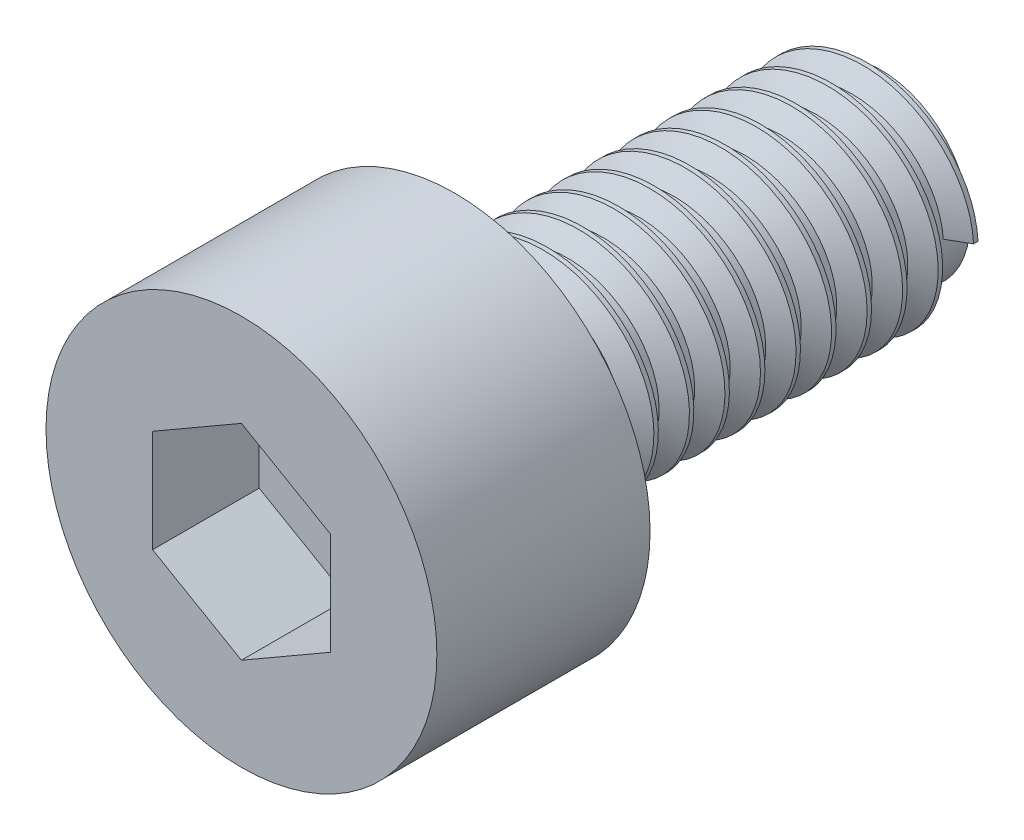
SolidWorks part; units mm, degrees
material "Cast Carbon Steel"
ref_plane "Front Plane" through (0, 0, 0) normal (0, 0, 1) x (1, 0, 0)
ref_plane "Top Plane" through (0, 0, 0) normal (0, 1, 0) x (1, 0, 0)
ref_plane "Right Plane" through (0, 0, 0) normal (1, 0, 0) x (0, 0, -1)
sketch "Sketch1" plane through (0, 0, 0) normal (0, 0, 1) x (1, 0, 0)
  circle A0 centre (0, 0) radius 2.75
  dimension "D1" = 5.5
extrude "Boss-Extrude1" add sketch "Sketch1" along normal blind 3
sketch "Sketch2" plane through (0, 0, 0) normal (0, 0, -1) x (-1, 0, 0)
  circle A0 centre (0, 0) radius 1.25
  dimension "D1" = 2.5
extrude "Boss-Extrude2" add sketch "Sketch2" along normal blind 6
sketch "Sketch3" plane through (0, 0, 3) normal (0, 0, 1) x (1, 0, 0)
  line L1 (0, 1.4434) -> (-1.25, 0.7217)
  line L2 (-1.25, 0.7217) -> (-1.25, -0.7217)
  line L3 (-1.25, -0.7217) -> (0, -1.4434)
  line L4 (0, -1.4434) -> (1.25, -0.7217)
  line L5 (1.25, -0.7217) -> (1.25, 0.7217)
  line L6 (1.25, 0.7217) -> (0, 1.4434)
  circle A0 centre (0, 0) radius 1.25 construction
  dimension "D1" = 2.5
extrude "Cut-Extrude1" cut sketch "Sketch3" against normal blind 1.5
thread "Thread1" pitch 0.5 method extrude profile "Thread Profile1" start angle 0, offset 0, length 6, pitch 0.5, diameter 2.5
ref_plane "Plane1" through (1.25, 0, -6) normal (0, -1, 0) x (1, 0, 0)
sketch "Thread Profile1" plane through (1.25, 0, -6) normal (0, -1, 0) x (1, 0, 0)
  line L0 (0, 0) -> (0, 0.5) construction
  line L1 (0, 0) -> (0.2706, 0.1562)
  line L2 (0.2706, 0.1562) -> (0.2706, 0.2187)
  line L3 (0.2706, 0.2187) -> (0, 0.375)
  line L4 (0.2706, 0.1875) -> (0, 0.1875) construction
  line L11 (0, 0) -> (0, 0.375)
  point P2 (0, 0)
  dimension "Pitch" = 0.5
  dimension "Profile_Angle" = 60
  dimension "Profile_Land" = 0.0625
  dimension "Profile_Height" = 0.2706
